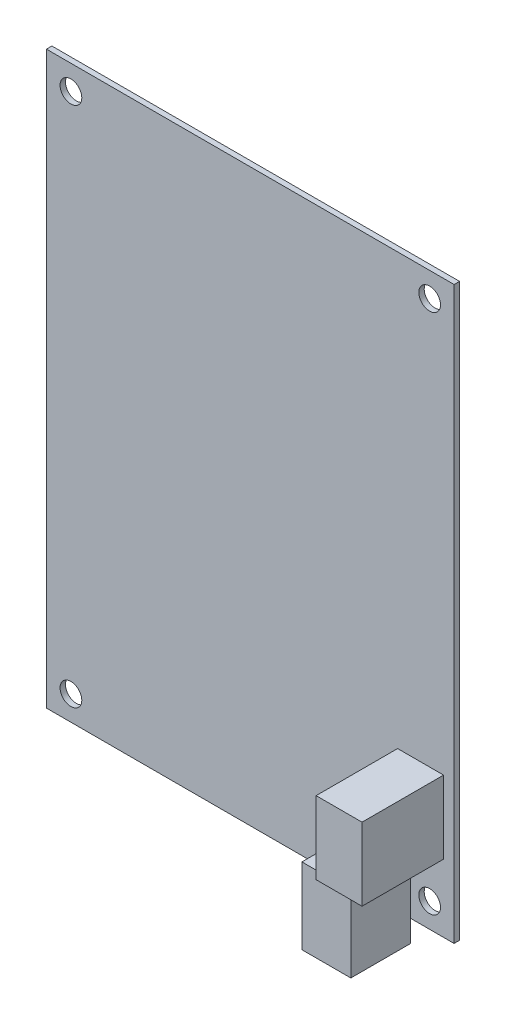
SolidWorks part; units mm, degrees
ref_plane "Plan de face" through (0, 0, 0) normal (0, 0, 1) x (1, 0, 0)
ref_plane "Plan de dessus" through (0, 0, 0) normal (0, 1, 0) x (1, 0, 0)
ref_plane "Plan de droite" through (0, 0, 0) normal (1, 0, 0) x (0, 0, -1)
sketch "Esquisse1" plane through (0, 0, 0) normal (0, 0, 1) x (1, 0, 0)
  line L1 (-37.5, 52.5) -> (37.5, 52.5)
  line L2 (-37.5, 52.5) -> (-37.5, -52.5)
  line L3 (-37.5, -52.5) -> (37.5, -52.5)
  line L4 (37.5, 52.5) -> (37.5, -52.5)
  line L5 (-37.5, 52.5) -> (37.5, -52.5) construction
  line L6 (-37.5, -52.5) -> (37.5, 52.5) construction
  point P0 (0, 0)
  dimension "D1" = 75
  dimension "D2" = 105
extrude "Boss.-Extru.1" add sketch "Esquisse1" along normal blind 1
sketch "Esquisse3" plane through (0, 0, 1) normal (0, 0, 1) x (1, 0, 0)
  line L0 (-37.5, 52.5) -> (-37.5, -52.5) construction
  line L1 (-37.5, -52.5) -> (37.5, -52.5) construction
  circle A0 centre (-33, -48) radius 2
  dimension "D1" = 4
  dimension "D2" = 4.5
  dimension "D3" = 4.5
extrude "Enlèv. mat.-Extru.1" cut sketch "Esquisse3" against normal up to next
mirror "Symétrie1" about plane through (0, 0, 0) normal (1, 0, 0) of "Enlèv. mat.-Extru.1"
mirror "Symétrie2" about plane through (0, 0, 0) normal (0, 1, 0) of "Symétrie1", "Enlèv. mat.-Extru.1"
sketch "Esquisse5" plane through (0, -52.5, 0) normal (0, -1, 0) x (1, 0, 0)
  line L0 (20.5, 1) -> (20.5, 12)
  line L1 (-37.5, 1) -> (37.5, 1) construction
  line L2 (20.5, 12) -> (29.5, 12)
  line L3 (29.5, 12) -> (29.5, 1)
  line L4 (29.5, 1) -> (20.5, 1)
  line L5 (37.5, 1) -> (37.5, 0) construction
  dimension "D1" = 11
  dimension "D2" = 9
  dimension "D3" = 8
extrude "Boss.-Extru.3" add sketch "Esquisse5" against normal blind 10
extrude "Boss.-Extru.4" add sketch "Esquisse5<2>" along normal blind 4
sketch "Esquisse5<2>" plane through (0, -52.5, 0) normal (0, -1, 0) x (1, 0, 0) same geometry as "Esquisse5"
sketch "Esquisse6" plane through (0, 0, 1) normal (0, 0, 1) x (1, 0, 0)
  line L0 (35.5617, -40.0335) -> (35.5617, -26.6381)
  line L1 (35.5617, -26.6381) -> (27.1098, -26.6381)
  line L2 (27.1098, -26.6381) -> (27.1098, -40.0335)
  line L3 (27.1098, -40.0335) -> (35.5617, -40.0335)
extrude "Boss.-Extru.5" add sketch "Esquisse6" along normal blind 15
